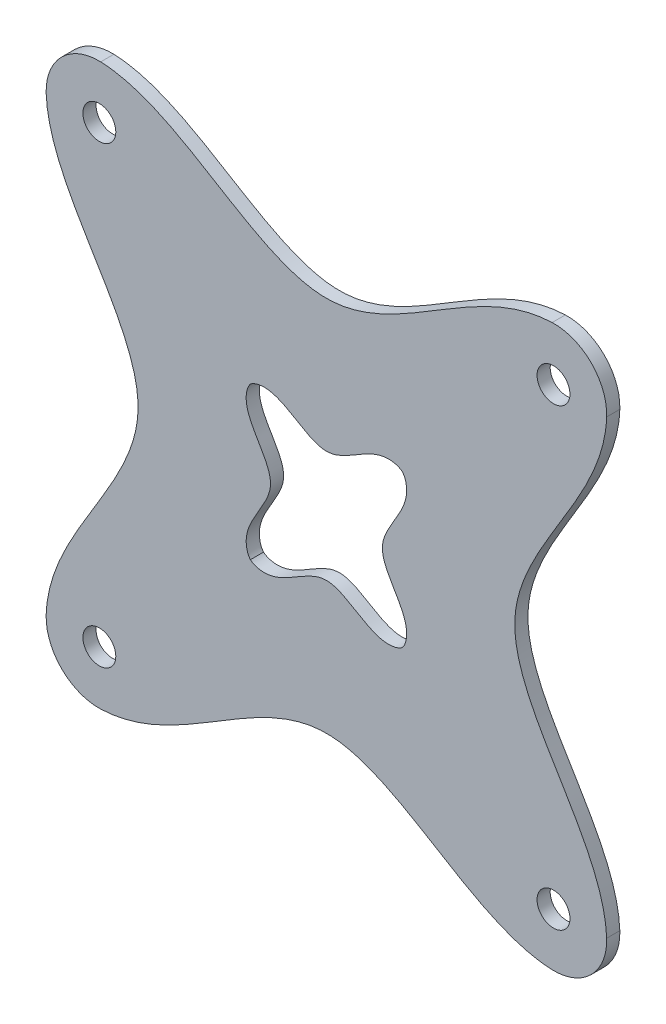
SolidWorks part; units mm, degrees
ref_plane "Front Plane" through (0, 0, 0) normal (0, 0, 1) x (1, 0, 0)
ref_plane "Top Plane" through (0, 0, 0) normal (0, 1, 0) x (1, 0, 0)
ref_plane "Right Plane" through (0, 0, 0) normal (1, 0, 0) x (0, 0, -1)
sketch "Sketch1" plane through (0, 0, 0) normal (0, 0, 1) x (1, 0, 0)
  line L1 (24.2824, -26.8224) -> (-24.2824, -26.8224) construction
  line L2 (26.8224, -24.2824) -> (26.8224, 24.2824) construction
  line L3 (24.2824, 26.8224) -> (-24.2824, 26.8224) construction
  line L4 (-26.8224, -24.2824) -> (-26.8224, 24.2824) construction
  line L5 (26.8224, -26.8224) -> (-26.8224, 26.8224) construction
  line L6 (26.8224, 26.8224) -> (-26.8224, -26.8224) construction
  line L7 (18.1737, 18.1737) -> (-18.1737, 18.1737) construction
  line L8 (18.1737, 18.1737) -> (18.1737, -18.1737) construction
  line L9 (18.1737, -18.1737) -> (-18.1737, -18.1737) construction
  line L10 (-18.1737, 18.1737) -> (-18.1737, -18.1737) construction
  line L11 (18.1737, 18.1737) -> (-18.1737, -18.1737) construction
  line L12 (18.1737, -18.1737) -> (-18.1737, 18.1737) construction
  spline S0 degree 3 poles (-26.0785, -26.0785) (-25.595, -26.4669) (-16.2014, -29.5054) (0, -7.6367) (16.2014, -29.5054) (25.595, -26.4669) (26.0785, -26.0785) knots 0.032767 0.032767 0.032767 0.032767 0.065534 0.5 0.934466 0.967233 0.967233 0.967233 0.967233
  spline S1 degree 3 poles (-26.0785, 26.0785) (-25.595, 26.4669) (-16.2014, 29.5054) (0, 7.6367) (16.2014, 29.5054) (25.595, 26.4669) (26.0785, 26.0785) knots 0.032767 0.032767 0.032767 0.032767 0.065534 0.5 0.934466 0.967233 0.967233 0.967233 0.967233
  spline S2 degree 3 poles (-26.0785, -26.0785) (-26.4669, -25.595) (-29.5054, -16.2014) (-7.6367, 0) (-29.5054, 16.2014) (-26.4669, 25.595) (-26.0785, 26.0785) knots 0.032767 0.032767 0.032767 0.032767 0.065534 0.5 0.934466 0.967233 0.967233 0.967233 0.967233
  spline S3 degree 3 poles (26.0785, -26.0785) (26.4669, -25.595) (29.5054, -16.2014) (7.6367, 0) (29.5054, 16.2014) (26.4669, 25.595) (26.0785, 26.0785) knots 0.032767 0.032767 0.032767 0.032767 0.065534 0.5 0.934466 0.967233 0.967233 0.967233 0.967233
  point P0 (0, 0)
  point P6 (0, 0)
  dimension "D1" = 53.6448
  dimension "D2" = 53.6448
extrude "Boss-Extrude1" add sketch "Sketch1" along normal blind 1.27
fillet "Fillet1" radius 5.08 3 edges at (26.0785, 26.0785, 0.635)
fillet "Fillet2" radius 5.08 3 edges at (-26.0785, -26.0785, 0.635)
fillet "Fillet3" radius 5.08 3 edges at (-26.0785, 26.0785, 0.635)
fillet "Fillet4" radius 5.08 3 edges at (26.0785, -26.0785, 0.635)
sketch "Sketch3" plane through (0, 0, 1.27) normal (0, 0, 1) x (1, 0, 0)
  line L0 (0, 0) -> (-38.6852, 0) construction
  line L1 (6.4389, 7.7089) -> (-6.4389, 7.7089) construction
  line L2 (7.7089, 6.4389) -> (7.7089, -6.4389) construction
  line L3 (6.4389, -7.7089) -> (-6.4389, -7.7089) construction
  line L4 (-7.7089, 6.4389) -> (-7.7089, -6.4389) construction
  line L5 (7.7089, 7.7089) -> (-7.7089, -7.7089) construction
  line L6 (7.7089, -7.7089) -> (-7.7089, 7.7089) construction
  line L7 (5.3975, 5.3975) -> (-5.3975, 5.3975) construction
  line L8 (5.3975, 5.3975) -> (5.3975, -5.3975) construction
  line L9 (5.3975, -5.3975) -> (-5.3975, -5.3975) construction
  line L10 (-5.3975, 5.3975) -> (-5.3975, -5.3975) construction
  line L11 (5.3975, 5.3975) -> (-5.3975, -5.3975) construction
  line L12 (5.3975, -5.3975) -> (-5.3975, 5.3975) construction
  line L13 (0, 0) -> (0, -29.8794) construction
  line L14 (0, 0) -> (21.9118, -21.9118) construction
  line L15 (0, 0) -> (-21.9118, -21.9118) construction
  line L16 (0, 0) -> (21.9118, 21.9118) construction
  line L17 (0, 0) -> (-21.9118, 21.9118) construction
  circle A0 centre (-21.9118, 21.9118) radius 1.5875
  circle A1 centre (21.9118, 21.9118) radius 1.5875
  circle A2 centre (21.9118, -21.9118) radius 1.5875
  circle A3 centre (-21.9118, -21.9118) radius 1.5875
  spline S0 degree 3 poles (-7.3369, -7.3369) (-7.0946, -7.54) (-4.4417, -8.4675) (0, -2.7094) (4.4417, -8.4675) (7.0946, -7.54) (7.3369, -7.3369) knots 0.055321 0.055321 0.055321 0.055321 0.110642 0.5 0.889358 0.944679 0.944679 0.944679 0.944679
  spline S1 degree 3 poles (-7.3369, 7.3369) (-7.0946, 7.54) (-4.4417, 8.4675) (0, 2.7094) (4.4417, 8.4675) (7.0946, 7.54) (7.3369, 7.3369) knots 0.055321 0.055321 0.055321 0.055321 0.110642 0.5 0.889358 0.944679 0.944679 0.944679 0.944679
  spline S2 degree 3 poles (-7.3369, 7.3369) (-7.54, 7.0946) (-8.4675, 4.4417) (-2.7094, 0) (-8.4675, -4.4417) (-7.54, -7.0946) (-7.3369, -7.3369) knots 0.055321 0.055321 0.055321 0.055321 0.110642 0.5 0.889358 0.944679 0.944679 0.944679 0.944679
  spline S3 degree 3 poles (7.3369, 7.3369) (7.54, 7.0946) (8.4675, 4.4417) (2.7094, 0) (8.4675, -4.4417) (7.54, -7.0946) (7.3369, -7.3369) knots 0.055321 0.055321 0.055321 0.055321 0.110642 0.5 0.889358 0.944679 0.944679 0.944679 0.944679
  point P0 (0, 0)
  point P6 (0, 0)
  dimension "D3" = 3.175
  dimension "D4" = 3.175
  dimension "D5" = 3.175
  dimension "D6" = 3.175
  dimension "D1" = 15.4178
  dimension "D2" = 15.4178
extrude "Cut-Extrude1" cut sketch "Sketch3" against normal through all
equation "\"HOLE SIZE\"= .125"
